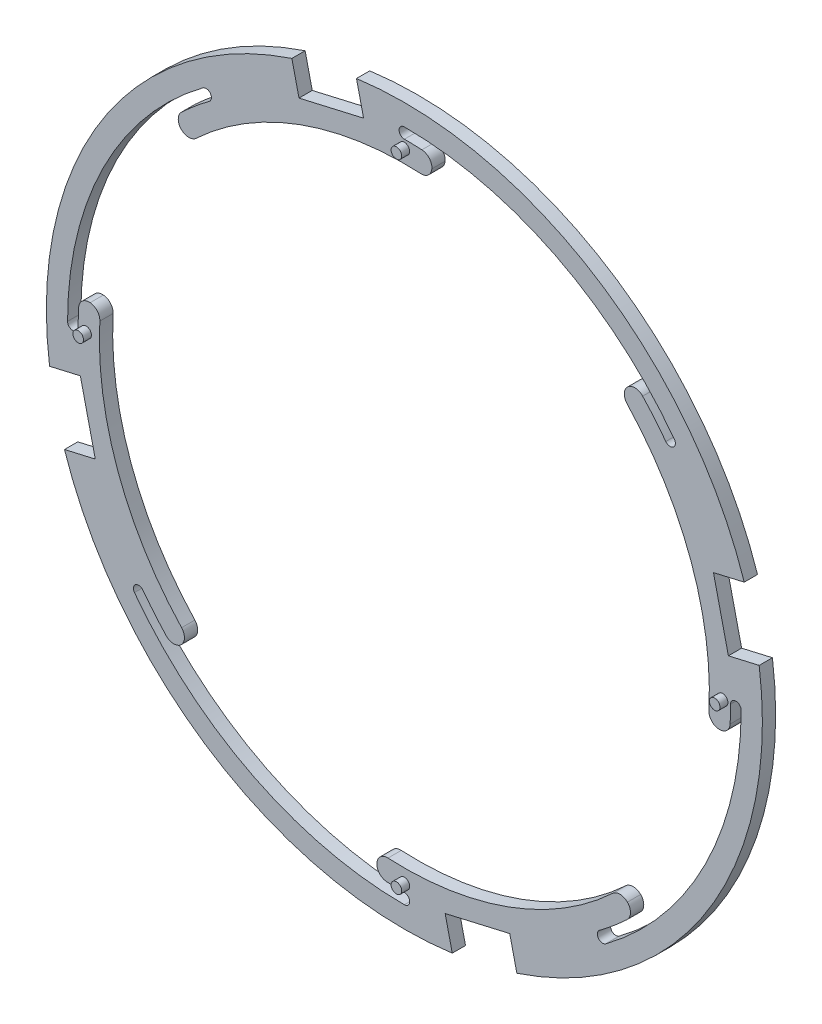
SolidWorks part; units mm, degrees
ref_plane "Piano frontale" through (0, 0, 0) normal (0, 0, 1) x (1, 0, 0)
ref_plane "Piano superiore" through (0, 0, 0) normal (0, 1, 0) x (1, 0, 0)
ref_plane "Piano destro" through (0, 0, 0) normal (1, 0, 0) x (0, 0, -1)
sketch "Schizzo1" plane through (0, 0, 0) normal (0, 0, 1) x (1, 0, 0)
  circle A0 centre (0, 0) radius 135
  dimension "D1" = 270
extrude "Estrusione-Estrusione1" add sketch "Schizzo1" along normal blind 5
sketch "Schizzo2" plane through (0, 0, 5) normal (0, 0, 1) x (1, 0, 0)
  circle A0 centre (0, 0) radius 115
extrude "Taglio-Estrusione1" cut sketch "Schizzo2" against normal through all
sketch "Schizzo3" plane through (0, 0, 5) normal (0, 0, 1) x (1, 0, 0)
  circle A0 centre (0, 0) radius 120 construction
  circle A1 centre (0, 120) radius 2
  dimension "D1" = 240
extrude "Estrusione-Estrusione2" add sketch "Schizzo3" along normal blind 3
pattern_circular "RipetizioneCircolare1" count 4 over 360 about axis through (0, 0, 5) along (0, 0, 1) of "Estrusione-Estrusione2"
sketch "Schizzo5" plane through (0, 0, 5) normal (0, 0, 1) x (1, 0, 0)
  line L0 (0, 0) -> (0, -125) construction
  line L1 (0, 0) -> (-100.1828, -74.7556) construction
  arc A1 (-100.1828, -74.7556) -> (0, -125) centre (0, 0) ccw construction
  arc A2 (-101.7858, -75.9517) -> (0, -127) centre (0, 0) ccw
  arc A3 (-98.5799, -73.5595) -> (0, -123) centre (0, 0) ccw
  arc A4 (-98.5799, -73.5595) -> (-101.7858, -75.9517) centre (-100.1828, -74.7556) ccw
  arc A5 (0, -127) -> (0, -123) centre (0, -125) ccw
  circle A6 centre (0, 0) radius 125 construction
  point P6 (-56.0382, -111.7351)
  dimension "D1" = 53.27
  dimension "D2" = 250
  dimension "D3" = 2
extrude "Taglio-Estrusione2" cut sketch "Schizzo5" against normal blind 10
pattern_circular "RipetizioneCircolare2" count 4 over 360 about axis through (0, 0, 5) along (0, 0, 1) of "Taglio-Estrusione2"
sketch "Schizzo14" plane through (0, 0, 0) normal (0, 0, 1) x (1, 0, 0)
  line L0 (0, 0) -> (0, 135) construction
  line L1 (0, 0) -> (-30.3684, 131.54) construction
  line L11 (-39.7361, 116.5484) -> (-45.3599, 140.9077)
  line L12 (-39.7361, 116.5484) -> (-15.3769, 122.1722)
  line L13 (-45.3599, 140.9077) -> (-21.0007, 146.5315)
  line L14 (-15.3769, 122.1722) -> (-21.0007, 146.5315)
  line L15 (-39.7361, 116.5484) -> (-21.0007, 146.5315) construction
  line L16 (-45.3599, 140.9077) -> (-15.3769, 122.1722) construction
  line L17 (-30.3684, 131.54) -> (-18.1888, 134.3518) construction
  circle A3 centre (0, 0) radius 135 construction
  circle A4 centre (0, 0) radius 135 construction
  dimension "D1" = 13
  dimension "D2" = 270
  dimension "D3" = 25
  dimension "D4" = 25
extrude "Taglio-Estrusione21" cut sketch "Schizzo14" along normal blind 8
pattern_circular "RipetizioneCircolare3" count 4 every 90 about axis through (0, 0, 0) along (0, 0, 1) of "Taglio-Estrusione21"
sketch "Schizzo15" plane through (0, 0, 5) normal (0, 0, 1) x (1, 0, 0)
  line L0 (0, 0) -> (-122.5319, 10.7202) construction
  line L1 (0, 0) -> (-86.9741, 86.9741) construction
  line L2 (-86.9741, 86.9741) -> (-81.3173, 81.3173)
  line L3 (-122.5319, 10.7202) -> (-114.5624, 10.0229)
  line L4 (0, 0) -> (0, 100.4036) construction
  arc A0 (-81.3173, 81.3173) -> (-114.5624, 10.0229) centre (0, 0) ccw
  arc A1 (-86.9741, 86.9741) -> (-122.5319, 10.7202) centre (0, 0) ccw
  dimension "D2" = 115
  dimension "D3" = 123
  dimension "D1" = 40
  dimension "D4" = 45
extrude "Taglio-Estrusione23" cut sketch "Schizzo15" against normal blind 10
pattern_circular "RipetizioneCircolare5" count 4 every 90 about axis through (0, 0, 5) along (0, 0, 1) of "Taglio-Estrusione23"
fillet "Raccordo1" radius 4 2 edges at (-114.5624, 10.0229, 2.5) (-122.5319, 10.7202, 2.5)
fillet "Raccordo2" radius 4 14 edges at (-81.3173, -81.3173, 2.5) (-86.9741, -86.9741, 2.5) (-10.0229, -114.5624, 2.5) (-10.7202, -122.5319, 2.5) (86.9741, -86.9741, 2.5) (81.3173, -81.3173, 2.5) (114.5624, -10.0229, 2.5) (122.5319, -10.7202, 2.5) (86.9741, 86.9741, 2.5) (81.3173, 81.3173, 2.5) (10.7202, 122.5319, 2.5) (10.0229, 114.5624, 2.5) (-81.3173, 81.3173, 2.5) (-86.9741, 86.9741, 2.5)
